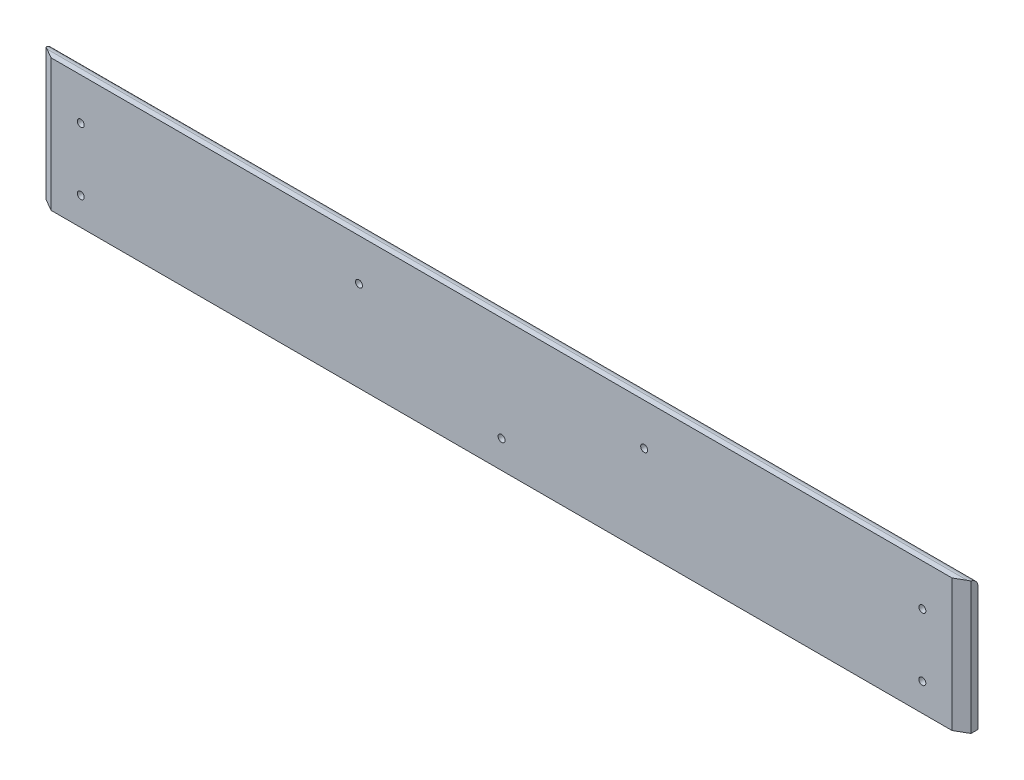
SolidWorks part; units mm, degrees
material "Настроенная пользователем пластмасса"
ref_plane "Спереди" through (0, 0, 0) normal (0, 0, 1) x (1, 0, 0)
ref_plane "Сверху" through (0, 0, 0) normal (0, 1, 0) x (1, 0, 0)
ref_plane "Справа" through (0, 0, 0) normal (1, 0, 0) x (0, 0, -1)
sketch "Эскиз1" plane through (0, 0, 0) normal (0, 0, 1) x (1, 0, 0)
  line L1 (-332.5, -47.5) -> (332.5, -47.5)
  line L2 (-332.5, -47.5) -> (-332.5, 47.5)
  line L3 (-332.5, 47.5) -> (332.5, 47.5)
  line L4 (332.5, -47.5) -> (332.5, 47.5)
  line L5 (0, 47.5) -> (0, -47.5) construction
  line L6 (-332.5, 0) -> (332.5, 0) construction
  point P0 (0, 0)
  dimension "D1" = 665
  dimension "D2" = 95
extrude "Бобышка-Вытянуть1" add sketch "Эскиз1" along normal mid plane 10
fillet "Скругление1" radius 6 1 edges at (0, 47.5, -5)
chamfer "Фаска1" distance 5 angle 60 2 edges at (332.5, 0, 5) (-332.5, 0, 5) first distance on face at (332.5, 8.5485, -0.0485) first distance on face at (-332.5, 8.5485, -0.0485)
sketch "Эскиз3" plane through (0, 0, 5) normal (0, 0, 1) x (1, 0, 0)
  line L0 (-323.8397, -47.5) -> (323.8397, -47.5) construction
  line L1 (-332.5, -47.5) -> (-332.5, 47.4161) construction
  line L2 (332.5, 47.4161) -> (332.5, -47.5) construction
  line L3 (0, -50) -> (0, 50) construction
  circle A0 centre (-302.5, -27.5) radius 2.5
  circle A1 centre (0, -27.5) radius 2.5
  circle A2 centre (302.5, -27.5) radius 2.5
  circle A3 centre (-302.5, 17.5) radius 2.5
  circle A4 centre (302.5, 17.5) radius 2.5
  circle A5 centre (-102.5, 17.5) radius 2.5
  circle A6 centre (102.5, 17.5) radius 2.5
  dimension "D1" = 5
  dimension "D2" = 20
  dimension "D3" = 30
  dimension "D4" = 30
  dimension "D5" = 45
  dimension "D6" = 200
  dimension "D7" = 200
extrude "Вырез-Вытянуть1" cut sketch "Эскиз3" against normal through all
chamfer "Фаска2" distance 2 angle 45 7 edges at (-300, -27.5, -5) (-300, 17.5, -5) (-100, 17.5, -5) (2.5, -27.5, -5) (105, 17.5, -5) (305, -27.5, -5) (305, 17.5, -5)
